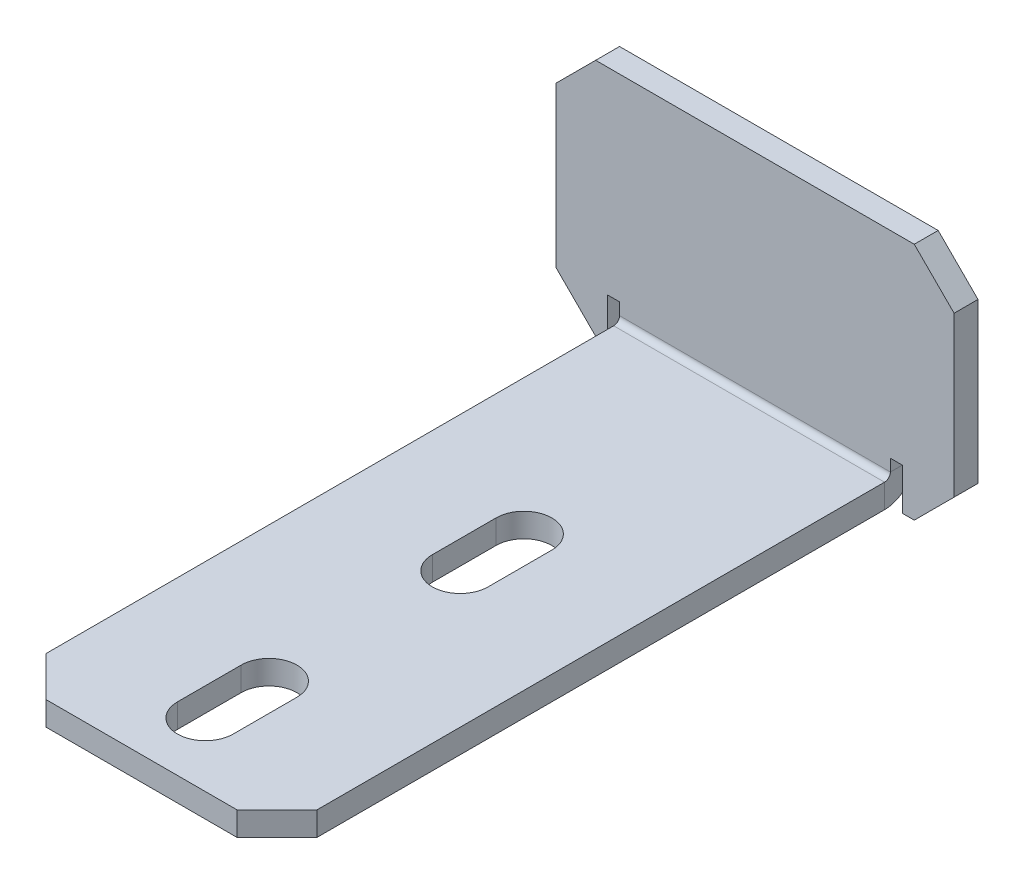
SolidWorks part; units mm, degrees
note: The reader was unsure of these and kept them because the rebuilt part matched: flange length of "边线-法兰1".
material "Q235-A"
ref_plane "前视基准面" through (0, 0, 0) normal (0, 0, 1) x (1, 0, 0)
ref_plane "上视基准面" through (0, 0, 0) normal (0, 1, 0) x (1, 0, 0)
ref_plane "右视基准面" through (0, 0, 0) normal (1, 0, 0) x (0, 0, -1)
sketch "草图1" plane through (0, 0, 0) normal (0, 0, 1) x (1, 0, 0)
  line L1 (0, 0) -> (50, 0)
  line L2 (0, 0) -> (0, 30)
  line L3 (0, 30) -> (50, 30)
  line L4 (50, 0) -> (50, 30)
  dimension "D1" = 30
  dimension "D2" = 50
base flange "基体-法兰1" sketch "草图1" thickness 3 reverse thickness direction no parameters "D1"=0.7366
edge flange "边线-法兰1" sketch "草图8" flange angle 90 flange length 80 flange position material inside bend radius 0.7366 thickness 3 relief rectangular parameters "D6"=10
sketch "草图8" plane through (0, 0, 0) normal (0, -1, 0) x (1, 0, 0)
  line L0 (0, 0) -> (50, 0) construction
  line L1 (8, 0) -> (42, 0)
  line L2 (8, 0) -> (8, 77)
  line L3 (8, 77) -> (42, 77)
  line L4 (42, 77) -> (42, 0)
  point P4 (43.3119, 0)
  point P6 (16.9187, 0)
  dimension "D1" = 8
  dimension "D2" = 8
bend "边线折弯1" bend radius 0.7366 bend angle 90 parameters "D5"=1
chamfer "倒角1" distance 5 angle 45 6 edges at (8, 1.5, 77) (42, 1.5, 77) (50, 0, -1.5) (0, 0, -1.5) (0, 30, -1.5) (50, 30, -1.5)
sketch "草图9" plane through (0, 3, 0) normal (0, 1, 0) x (1, 0, 0)
  line L0 (25, -77) -> (25, 16.9847) construction
  line L1 (37, -77) -> (13, -77) construction
  line L2 (25, -29) -> (25, -37) construction
  line L3 (28.5, -29) -> (28.5, -37)
  line L4 (21.5, -29) -> (21.5, -37)
  line L5 (25, -69) -> (25, -61) construction
  line L6 (21.5, -69) -> (21.5, -61)
  line L7 (28.5, -69) -> (28.5, -61)
  arc A0 (28.5, -29) -> (21.5, -29) centre (25, -29) ccw
  arc A1 (21.5, -37) -> (28.5, -37) centre (25, -37) ccw
  arc A2 (21.5, -69) -> (28.5, -69) centre (25, -69) ccw
  arc A3 (28.5, -61) -> (21.5, -61) centre (25, -61) ccw
  point P6 (25, -33)
  point P12 (25, -65)
  dimension "D1" = 7
  dimension "D2" = 8
  dimension "D3" = 8
  dimension "D4" = 7
  dimension "D5" = 12
  dimension "D6" = 32
extrude "切除-拉伸1" cut sketch "草图9" against normal blind 10 normal cut yes
sketch "折弯-线1" [suppressed] plane through (0, 0, 0) normal (0, 1, 0) x (1, 0, 0)
sketch "边界框1" [suppressed] plane through (0, 0, 0) normal (0, 1, 0) x (1, 0, 0)
sheet metal parameters "钣金1" thickness 3 parameters "D1"=0.7366
flat pattern "平板型式1" [suppressed]
sketch "折弯-线2" plane through (0, 0, 0) normal (0, 1, 0) x (1, 0, 0)
sketch3d "边界框2" [suppressed]
  line L0 (0, 0, 0) -> (-50, 0, 0) construction
  line L1 (0, 30, 0) -> (-50, 30, 0) construction
  line L2 (0, 0, 0) -> (0, 30, 0) construction
  line L3 (-50, 0, 0) -> (-50, 30, 0) construction
sheet metal parameters "钣金2" thickness 3 parameters "D1"=0.7366
flat pattern "平板型式1"
sketch "折弯-线2" plane through (0, 0, 0) normal (0, 0, 1) x (1, 0, 0)
  line L0 (8, 1.98) -> (42, 1.98) construction
  line L1 (8, 1.98) -> (42, 1.98) construction
sketch3d "边界框2" [suppressed]
  line L0 (50, 30, 0) -> (50, -76.04, 0) construction
  line L1 (0, 30, 0) -> (0, -76.04, 0) construction
  line L2 (50, 30, 0) -> (0, 30, 0) construction
  line L3 (50, -76.04, 0) -> (0, -76.04, 0) construction
bend of the flat pattern "展平-<边线折弯1>1"
sheet metal parameters "钣金3" thickness 3 parameters "D1"=0.7366
flat pattern "平板型式1"
sketch "折弯-线2" plane through (0, 0, 0) normal (0, 0, 1) x (1, 0, 0)
  line L0 (8, 1.98) -> (42, 1.98) construction
  line L1 (8, 1.98) -> (42, 1.98) construction
sketch3d "边界框2" [suppressed]
  line L0 (50, 30, 0) -> (50, -76.04, 0) construction
  line L1 (0, 30, 0) -> (0, -76.04, 0) construction
  line L2 (50, 30, 0) -> (0, 30, 0) construction
  line L3 (50, -76.04, 0) -> (0, -76.04, 0) construction
bend of the flat pattern "展平-<边线折弯1>1"
